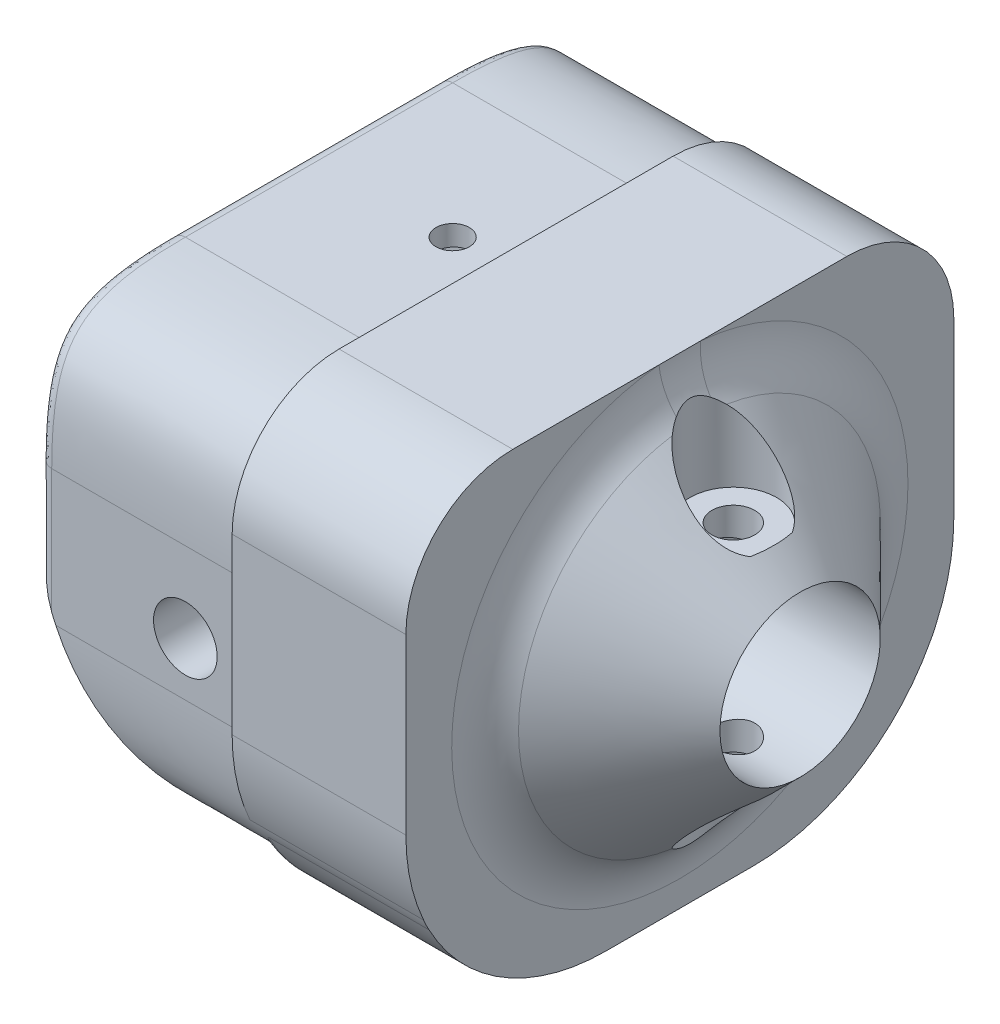
SolidWorks part; units mm, degrees
ref_plane "Alzado" through (0, 0, 0) normal (0, 0, 1) x (1, 0, 0)
ref_plane "Planta" through (0, 0, 0) normal (0, 1, 0) x (1, 0, 0)
ref_plane "Vista lateral" through (0, 0, 0) normal (1, 0, 0) x (0, 0, -1)
sketch "Croquis1" plane through (0, 0, 0) normal (0, 0, 1) x (1, 0, 0)
  line L0 (0, 18.4016) -> (0, -18.6637) construction
  line L1 (-11.5, -11.5336) -> (11.5, -11.5336)
  line L2 (-11.5, -11.5336) -> (-11.5, 11.5336)
  line L3 (-11.5, 11.5336) -> (11.5, 11.5336)
  line L4 (11.5, -11.5336) -> (11.5, 11.5336)
  line L5 (-11.5, -11.5336) -> (11.5, 11.5336) construction
  line L6 (-11.5, 11.5336) -> (11.5, -11.5336) construction
  line L7 (0, 0) -> (-4.878, 15.4712) construction
  line L8 (0, 0) -> (6.4996, 12.4855)
  circle A0 centre (0, 0) radius 11.5
  point P0 (0, 0)
  dimension "D1" = 23
  dimension "D2" = 17.5
  dimension "D3" = 45
sketch "Croquis3" plane through (0, 0, 0) normal (0, 0, 1) x (1, 0, 0)
  line L0 (-13, 16) -> (17, 16)
  line L6 (17, -14) -> (-13, -14)
  line L7 (-13, -14) -> (-13, 16)
  line L9 (17, 16) -> (17, -14)
  line L10 (14, 0) -> (-65.7308, 0) construction
  circle A0 centre (0, 0) radius 11 construction
  circle A1 centre (0, 0) radius 14 construction
  circle A2 centre (0, 0) radius 13 construction
  dimension "D1" = 22
  dimension "D2" = 28
  dimension "D3" = 26
  dimension "D4" = 30
  dimension "D5" = 14
  dimension "D6" = 30
  dimension "D7" = 13
extrude "Saliente-Extruir1" add sketch "Croquis3" along normal mid plane 40
sketch "Croquis4" plane through (0, 0, 0) normal (0, 0, 1) x (1, 0, 0)
  line L0 (-13, 16) -> (17, 16)
  line L6 (17, -14) -> (-13, -14)
  line L9 (17, 16) -> (17, -14)
  line L10 (14, 0) -> (-65.7308, 0) construction
  line L11 (5.5555, -18.1712) -> (-6.9071, 22.5922) construction
  line L12 (0, -28.2293) -> (0, 27.04) construction
  line L13 (0, 0) -> (11.2348, 21.1297) construction
  line L14 (6.0092, 11.3017) -> (5.2816, 9.9332)
  line L15 (3.2892, -10.7584) -> (3.7424, -12.2407)
  circle A0 centre (0, 0) radius 11.25
  circle A1 centre (0, 0) radius 14 construction
  circle A2 centre (0, 0) radius 12.8
  dimension "D1" = 22.5
  dimension "D2" = 28
  dimension "D3" = 25.6
  dimension "D4" = 30
  dimension "D5" = 14
  dimension "D6" = 30
  dimension "D8" = 17
  dimension "D9" = 45
extrude "Cortar-Extruir6" cut sketch "Croquis4" against normal mid plane 11.5 contours A0 | L14 A2 L15 A0 region at (5.3649, 10.7666, 0) region at (0, 0, 0)
sketch "Croquis5" plane through (0, 0, 0) normal (0, 0, 1) x (1, 0, 0)
  circle A0 centre (0, 0) radius 2.3813
  dimension "D1" = 4.7625
extrude "Cortar-Extruir7" cut sketch "Croquis5" against normal mid plane 71.5
sketch "Croquis7" plane through (0, 0, 20) normal (0, 0, 1) x (1, 0, 0)
  line L1 (-13, -14) -> (-11, -14)
  line L2 (-13, -14) -> (-13, 16)
  line L3 (-13, 16) -> (-11, 16)
  line L4 (-11, -14) -> (-11, 16)
  line L8 (17, 16) -> (-13, 16) construction
  line L9 (-13, -14) -> (17, -14) construction
  line L10 (-13, 16) -> (-13, -14) construction
  dimension "D1" = 2
extrude "Cortar-Extruir8" cut sketch "Croquis7" against normal blind 71.5
sketch "Croquis8" plane through (0, 0, 0) normal (0, 0, 1) x (1, 0, 0)
  line L0 (-3.8008, 12.432) -> (3.8008, -12.432)
  line L1 (0, 17.2152) -> (0, -15.7835) construction
  line L2 (-3.8008, 12.432) -> (-19.1017, 7.754)
  line L3 (-19.1017, 7.754) -> (-11.5, -17.1099)
  line L4 (-11.5, -17.1099) -> (3.8008, -12.432)
  circle A0 centre (0, 0) radius 13
  dimension "D1" = 26
  dimension "D2" = 17
  dimension "D3" = 16
extrude "Cortar-Extruir9" cut sketch "Croquis8" against normal mid plane 11.5 contours L1 L0 A0 | L4 L0 L2 L3 region at (-5.9597, -0.8907, 0)
fillet "Redondeo1" radius 10 4 edges at (3, 16, -20) (3, 16, 20) (3, -14, 20) (3, -14, -20) conic rho 0.6
ref_plane "Plano2" through (10, 0, 0) normal (1, 0, 0) x (0, 0, -1)
sketch "Croquis10" plane through (0, 0, 0) normal (0, 0, 1) x (1, 0, 0)
  line L1 (13.5, 16.5) -> (-13.5, 16.5)
  line L2 (13.5, 16.5) -> (13.5, -16.5)
  line L3 (13.5, -16.5) -> (-13.5, -16.5)
  line L4 (-13.5, 16.5) -> (-13.5, -16.5)
  line L5 (13.5, 16.5) -> (-13.5, -16.5) construction
  line L6 (13.5, -16.5) -> (-13.5, 16.5) construction
  line L7 (0, 0) -> (-2, 0)
  line L8 (0, 0) -> (0, -16.5)
  line L9 (0, -16.5) -> (-2, -16.5)
  line L10 (-2, 0) -> (-2, -16.5)
  circle A0 centre (0, 0) radius 13.5
  point P0 (0, 0)
  dimension "D1" = 27
  dimension "D2" = 33
  dimension "D3" = 2
extrude "Cortar-Extruir10" cut sketch "Croquis10" against normal mid plane 52 contours A0 L4 L3 L10 region at (-9.2133, -12.5997, 0)
sketch "Croquis11" plane through (10, 0, 0) normal (1, 0, 0) x (0, 0, -1)
  line L0 (-12.5, 17) -> (12.5, 17)
  line L1 (20.5, 9) -> (20.5, -4)
  line L2 (5.5, -19) -> (-5.5, -19)
  line L3 (-20.5, -4) -> (-20.5, 9)
  line L4 (0, -28.6314) -> (0, 23.5987) construction
  line L5 (-10, 16) -> (10, 16) construction
  line L6 (-10, -14) -> (10, -14) construction
  arc A0 (20.5, -4) -> (5.5, -19) centre (5.5, -4) cw
  arc A1 (-5.5, -19) -> (-20.5, -4) centre (-5.5, -4) cw
  arc A2 (12.5, 17) -> (20.5, 9) centre (12.5, 9) cw
  arc A3 (-12.5, 17) -> (-20.5, 9) centre (-12.5, 9) ccw
  point P17 (20.5, 17)
  point P20 (-20.5, 17)
  dimension "D4" = 15
  dimension "D5" = 8
  dimension "D1" = 41
  dimension "D2" = 1
  dimension "D3" = 5
extrude "Saliente-Extruir3" add sketch "Croquis11" along normal up to surface (7 mm away) and the other way blind 6 contours A3 L0 A2 L1 A0 L2 A1 L3 up to face at (17, -0.25, 2.5)
sketch "Croquis12" plane through (17, 0, 0) normal (1, 0, 0) x (0, 0, -1)
  line L0 (0, 22.8287) -> (0, -36.156) construction
  line L1 (-7, 20) -> (7, 20)
  line L2 (-25, 2) -> (-25, -25)
  line L3 (-5, -45) -> (5, -45)
  line L4 (25, 2) -> (25, -25)
  arc A0 (7, 20) -> (25, 2) centre (7, 2) cw
  arc A1 (-7, 20) -> (-25, 2) centre (-7, 2) ccw
  arc A2 (5, -45) -> (25, -25) centre (5, -25) ccw
  arc A3 (-25, -25) -> (-5, -45) centre (-5, -25) ccw
  point P9 (25, 20)
  point P12 (-25, 20)
  point P17 (-25, -45)
  dimension "D4" = 18
  dimension "D5" = 20
  dimension "D1" = 50
  dimension "D2" = 65
  dimension "D3" = 20
sketch "Croquis15" plane through (0, 0, 20) normal (0, 0, 1) x (1, 0, 0)
  line L0 (-13.1973, 3.3183) -> (25.1973, 3.3183) construction
  line L1 (-11, -4) -> (-11, 6) construction
  line L2 (-11, -4) -> (-11, 0.0133)
  line L3 (-11, 3.3183) -> (-11, 6)
  line L9 (17, -10.1738) -> (4, -10.1737)
  line L10 (4, -10.1737) -> (4, -4)
  line L11 (4, -4) -> (-11, -4)
  line L12 (-11, -4) -> (-11, -7.8262)
  line L13 (-2, -13.351) -> (-2, -14)
  line L14 (-2, -14) -> (4, -14)
  line L15 (4, -14) -> (4, -11.0219)
  line L16 (4, -11.0219) -> (17, -11.0165)
  line L17 (17, -11.0165) -> (17, -10.1738)
  line L18 (17, -10.1738) -> (4, -10.1737)
  line L19 (4, -10.1737) -> (4, -4)
  line L20 (4, -4) -> (-11, -4)
  line L21 (-11, -4) -> (-11, -7.8262)
  line L22 (-2, -13.351) -> (-2, -14)
  line L23 (-2, -14) -> (4, -14)
  line L24 (4, -14) -> (4, -11.0219)
  line L25 (4, -11.0219) -> (17, -11.0165)
  line L31 (17, -11.0165) -> (17, -10.1738)
  arc A0 (-11, 0.0133) -> (23.3183, 3.3183) centre (6, 3.3183) ccw
  arc A1 (-11, -7.8262) -> (-2, -13.351) centre (0, 0) ccw
  arc A2 (-11, -7.8262) -> (-2, -13.351) centre (0, 0) ccw
  line M15 (-11, 6) -> (-11, -4)
  dimension "D2" = 3.3183
  dimension "D3" = 6
  dimension "D1" = 0
extrude "Cortar-Extruir11" cut sketch "Croquis15" against normal blind 55 contours A0 M15 | L21 A2 L22 L23 A0 region at (-10.5925, -2.7675, 20) region at (-6.3469, -9.7063, 20)
sketch "Croquis19" plane through (0, 16, 0) normal (0, 1, 0) x (1, 0, 0)
  circle A0 centre (0, 0) radius 1.25
  dimension "D1" = 2.5
extrude "Cortar-Extruir13" cut sketch "Croquis19" against normal blind 10
sketch "Croquis20" plane through (0, 0, 0) normal (0, 0, 1) x (1, 0, 0)
  circle A0 centre (0, 0) radius 14.5
  dimension "D1" = 29
extrude "Cortar-Extruir14" cut sketch "Croquis20" against normal mid plane 14
fillet "Redondeo17" radius 1 3 edges at (4, -16.8516, -13.2353) (4, -16.8516, 13.2353) (4, -19, 0)
fillet "Redondeo18" radius 1 5 edges
sketch "Croquis21" plane through (17, 0, 0) normal (1, 0, 0) x (0, 0, -1)
  circle A0 centre (0, 0) radius 6.5
  dimension "D1" = 13
extrude "Cortar-Extruir15" cut sketch "Croquis21" against normal blind 1
sketch "Croquis22" plane through (0, 0, 0) normal (0, 1, 0) x (1, 0, 0)
  line L0 (0, 0) -> (40.3064, 0) construction
  line L1 (17, 6) -> (26, 6)
  line L2 (17, 5) -> (17, 25) construction
  line L3 (17, -5) -> (17, 5) construction
  line L4 (26, 6) -> (17, 15)
  line L5 (17, 15) -> (17, 6)
  dimension "D1" = 6
  dimension "D2" = 9
revolve "Revolución1" add sketch "Croquis22" angle 360 about L0
fillet "Redondeo24" radius 5 1 edges at (17, 0, 15)
sketch "Croquis23" plane through (0, 0, 0) normal (0, 1, 0) x (1, 0, 0)
  line L0 (0, 0) -> (33.2634, 0) construction
  circle A0 centre (21, 0) radius 1.6
  dimension "D1" = 3.2
  dimension "D2" = 21
extrude "Cortar-Extruir16" cut sketch "Croquis23" against normal mid plane 55
sketch "Croquis24" plane through (0, 17, 0) normal (0, 1, 0) x (1, 0, 0)
  line L0 (0, 0) -> (33.934, 0) construction
  circle A0 centre (21, 0) radius 3.25
  dimension "D1" = 6.5
extrude "Cortar-Extruir17" cut sketch "Croquis24" against normal blind 9
mirror "Simetría1" about plane through (0, 0, 0) normal (0, 1, 0) of "Cortar-Extruir17"
